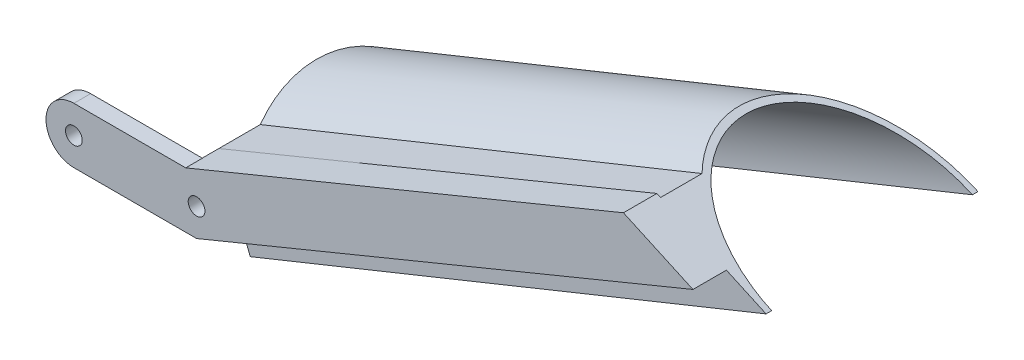
SolidWorks part; units mm, degrees
ref_plane "Front Plane" through (0, 0, 0) normal (0, 0, 1) x (1, 0, 0)
ref_plane "Top Plane" through (0, 0, 0) normal (0, 1, 0) x (1, 0, 0)
ref_plane "Right Plane" through (0, 0, 0) normal (1, 0, 0) x (0, 0, -1)
sketch "Sketch1" plane through (0, 0, 0) normal (0, 0, 1) x (1, 0, 0)
  line L0 (0, 0) -> (22, 0) construction
  line L1 (0, 5) -> (22, 5)
  line L2 (0, -5) -> (22, -5)
  line L3 (21.5213, 1.4216) -> (23.9914, -4.5863) construction
  line L4 (46.409, 15.8375) -> (51.4959, 17.929) construction
  line L5 (20.05, 5) -> (46.409, 15.8375)
  line L6 (51.4959, 17.929) -> (53.6145, 12.7761) construction
  line L7 (53.3599, 12.6714) -> (58.8728, 10.1603)
  line L8 (46.409, 15.8375) -> (53.3599, 12.6714)
  line L9 (48.359, 5.8375) -> (58.8728, 10.1603)
  line L11 (48.359, 5.8375) -> (22, -5)
  arc A0 (0, 5) -> (0, -5) centre (0, 0) ccw
  arc A1 (22, -5) -> (22, 5) centre (22, 0) ccw
  circle A2 centre (0, 0) radius 1.5
  circle A3 centre (22, 0) radius 1.5
  point P3 (11, 0)
  dimension "D2" = 10
  dimension "D11" = 3
  dimension "D1" = 22
  dimension "D3" = 157.65
  dimension "D4" = 1.95
  dimension "D5" = 34
  dimension "D9" = 5.5
extrude "Boss-Extrude1" add sketch "Sketch1" along normal blind 3 contours A1 L1 A0 L2 A3 A2 | A1 L8 L1 region at (10.9566, 0.015, 0) region at (39.2383, 7.2413, 0)
sketch "草图1" plane through (0, 0, 3) normal (0, 0, 1) x (1, 0, 0)
  line L5 (46.409, 15.8375) -> (58.8728, 10.1603)
  line L7 (98.5446, 37.273) -> (111.0084, 31.5958)
  line L8 (46.409, 15.8375) -> (98.5446, 37.273)
  line L17 (58.8728, 10.1603) -> (111.0084, 31.5958)
extrude "凸台-拉伸1" add sketch "草图1" against normal up to surface (3 mm away) up to face at (23.5, 0, 0)
sketch "草图2" plane through (0, 0, 0) normal (0, 0, -1) x (-1, 0, 0)
  line L0 (-22, 0) -> (0, 0)
  line L1 (0, 0) -> (-6.7184, -16.6453)
  line L2 (-6.7184, -16.6453) -> (-25.6368, -9.0032)
  circle A0 centre (-22, 0) radius 9.71
  circle A1 centre (0, 0) radius 17.95
ref_plane "基准面1" through (6.7231, -16.6434, 0) normal (-0.3745, 0.9272, 0) x (0.9272, 0.3745, 0)
sketch "草图3" plane through (0, 0, 0) normal (0, 0, -1) x (-1, 0, 0)
  line L0 (-22, 0) -> (-27.5784, -13.8097)
ref_plane "基准面2" through (18.9137, 7.6402, 0) normal (-0.9272, -0.3745, 0) x (0.3745, -0.9272, 0)
ref_plane "基准面3" through (0, 0, 3) normal (0, 0, 1) x (1, 0, 0)
ref_axis "基准轴1" through (29.9958, -19.794, 3) along (-0.3745, 0.9272, 0)
ref_axis "基准轴2" through (116.8088, 27.8257, 3) along (-0.9272, -0.3745, 0)
ref_point "点1"
sketch "草图4" plane through (0, 0, 0) normal (0, 0, -1) x (-1, 0, 0)
  line L0 (-111.0084, 31.5958) -> (-98.5446, 37.273)
  line L1 (-111.0084, 31.5958) -> (-23.7321, -4.2879)
  line L2 (-98.5446, 37.273) -> (-19.9902, 4.9754)
  line L4 (-19.9902, 4.9754) -> (-21.0636, 2.318)
  line L6 (-22.9364, -2.318) -> (-23.7321, -4.2879)
  arc A0 (-21.0636, 2.318) -> (-22.9364, -2.318) centre (-22, 0) ccw
extrude "凸台-拉伸2" add sketch "草图4" along normal blind 3
sketch "草图5" plane through (18.9137, 7.6402, 0) normal (-0.9272, -0.3745, 0) x (0.3745, -0.9272, 0)
  line L0 (17.95, -3) -> (17.95, -4)
  line L1 (17.95, -41) -> (17.95, -40)
  line L2 (17.95, -3) -> (2.874, -3)
  line L3 (2.874, -3) -> (2.874, -10.4365)
  arc A0 (17.95, -4) -> (17.95, -40) centre (17.95, -22) ccw
  arc A1 (2.874, -10.4365) -> (17.95, -41) centre (17.95, -22) ccw
extrude "凸台-拉伸3" add sketch "草图5" against normal up to surface (99.745 mm away) up to face at (104.7765, 34.4344, 0)
